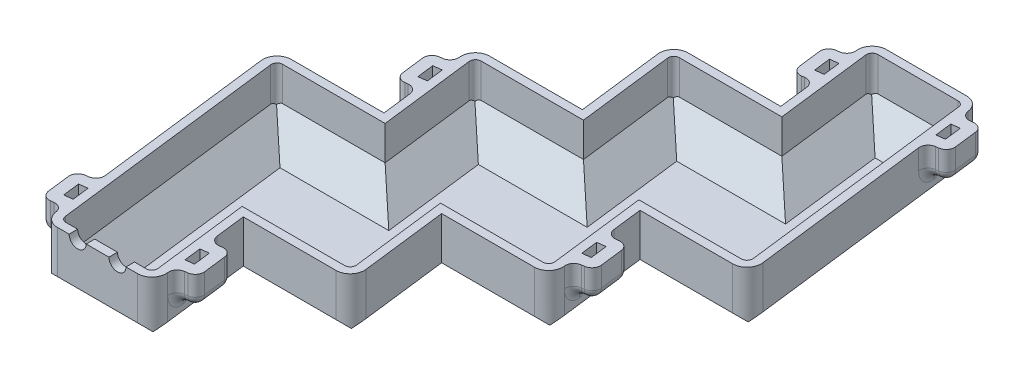
SolidWorks part; units mm, degrees
ref_plane "Front Plane" through (0, 0, 0) normal (0, 0, 1) x (1, 0, 0)
ref_plane "Top Plane" through (0, 0, 0) normal (0, 1, 0) x (1, 0, 0)
ref_plane "Right Plane" through (0, 0, 0) normal (1, 0, 0) x (0, 0, -1)
sketch "Sketch1" plane through (0, 0, 0) normal (0, 1, 0) x (1, 0, 0)
  line L12 (-24.7822, 46.1566) -> (13.5006, 46.1566)
  line L17 (-24.7822, 46.1566) -> (-13.5006, -46.1566)
  line L18 (13.5006, 46.1566) -> (24.7822, -46.1566)
  line L19 (-13.5006, -46.1566) -> (24.7822, -46.1566)
  line L20 (-5.6408, 46.1566) -> (5.6408, -46.1566) construction
  line L21 (58.6781, -10.261) -> (20.3954, -10.261)
  line L22 (58.6781, -10.261) -> (47.3965, 82.0522)
  line L23 (20.3954, -10.261) -> (9.1138, 82.0522)
  line L24 (47.3965, 82.0522) -> (9.1138, 82.0522)
  line L25 (39.5367, -10.261) -> (28.2551, 82.0522) construction
  line L26 (-58.6781, 10.261) -> (-20.3954, 10.261)
  line L27 (-58.6781, 10.261) -> (-47.3965, -82.0522)
  line L28 (-20.3954, 10.261) -> (-9.1138, -82.0522)
  line L29 (-47.3965, -82.0522) -> (-9.1138, -82.0522)
  line L30 (-39.5367, 10.261) -> (-28.2551, -82.0522) construction
  line L31 (-10.8449, -43.1566) -> (21.3932, -43.1566) construction
  line L32 (-10.8449, -43.1566) -> (-21.3932, 43.1566) construction
  line L33 (21.3932, -43.1566) -> (10.8449, 43.1566) construction
  line L34 (-21.3932, 43.1566) -> (10.8449, 43.1566) construction
  line L35 (-20.3954, 10.261) -> (20.3954, -10.261) construction
  line L36 (5.2742, -43.1566) -> (21.156, -41.2157) construction
  line L37 (-92.574, -25.6346) -> (-54.2913, -25.6346)
  line L38 (-92.574, -25.6346) -> (-81.2924, -117.9478)
  line L39 (-54.2913, -25.6346) -> (-43.0097, -117.9478)
  line L40 (-81.2924, -117.9478) -> (-43.0097, -117.9478)
  line L41 (-13.5006, -46.1566) -> (-54.2913, -25.6346) construction
  point P7 (0, 0)
  point P20 (-5.2742, 43.1566)
  point P21 (5.2742, -43.1566)
  point P26 (16.119, 0)
  point P27 (0, 0)
  point P28 (-33.8959, -35.8956)
  point P36 (-33.8959, -35.8956)
  dimension "D1" = 93
  dimension "D2" = 32
  dimension "D3" = 200
  dimension "D4" = 3
  dimension "D5" = 3
  dimension "D6" = 85
extrude "Boss-Extrude1" add sketch "Sketch1" along normal blind 25
sketch "Sketch4" plane through (0, 25, 0) normal (0, 1, 0) x (1, 0, 0)
  line L0 (-10.8449, -43.1566) -> (21.3932, -43.1566)
  line L1 (-10.8449, -43.1566) -> (-21.3932, 43.1566)
  line L2 (21.3932, -43.1566) -> (10.8449, 43.1566)
  line L3 (-21.3932, 43.1566) -> (10.8449, 43.1566)
  line L4 (23.051, -7.261) -> (55.2891, -7.261)
  line L5 (23.051, -7.261) -> (12.5027, 79.0522)
  line L6 (55.2891, -7.261) -> (44.7408, 79.0522)
  line L7 (12.5027, 79.0522) -> (44.7408, 79.0522)
  line L8 (28.6217, 79.0522) -> (39.1701, -7.261) construction
  line L9 (-55.2891, 7.261) -> (-23.051, 7.261)
  line L10 (-55.2891, 7.261) -> (-44.7408, -79.0522)
  line L11 (-23.051, 7.261) -> (-12.5027, -79.0522)
  line L12 (-44.7408, -79.0522) -> (-12.5027, -79.0522)
  line L13 (-39.1701, 7.261) -> (-28.6217, -79.0522) construction
  line L14 (-58.6781, 10.261) -> (-20.3954, 10.261) construction
  line L15 (-58.6781, 10.261) -> (-47.3965, -82.0522) construction
  line L16 (47.3965, 82.0522) -> (9.1138, 82.0522) construction
  line L17 (20.3954, -10.261) -> (9.1138, 82.0522) construction
  line L18 (-23.051, 7.261) -> (-17.0064, 7.261)
  line L19 (-10.8449, -43.1566) -> (-16.8895, -43.1566)
  line L20 (23.051, -7.261) -> (17.0064, -7.261)
  line L21 (10.8449, 43.1566) -> (16.8895, 43.1566)
  line L22 (-89.185, -28.6346) -> (-56.947, -28.6346)
  line L23 (-89.185, -28.6346) -> (-78.6367, -114.9478)
  line L24 (-56.947, -28.6346) -> (-46.3986, -114.9478)
  line L25 (-78.6367, -114.9478) -> (-46.3986, -114.9478)
  line L26 (-56.947, -28.6346) -> (-50.9023, -28.6346)
  line L27 (-44.7408, -79.0522) -> (-50.7854, -79.0522)
  line L29 (-92.574, -25.6346) -> (-54.2913, -25.6346) construction
  dimension "D1" = 3
  dimension "D2" = 3
  dimension "D3" = 3
  dimension "D4" = 3
  dimension "D5" = 3
extrude "Cut-Extrude1" cut sketch "Sketch4" against normal blind 22 contours L10 L12 L11 L9 | L19 L1 L18 L11 | L3 L1 L0 L2 | L7 L5 L4 L6 | L21 L2 L20 L5 | L23 L25 L24 L22 | L27 L10 L26 L24
chamfer "Chamfer1" distance 10 angle 45 32 edges at (39.5367, 0, 10.261) (22.5888, 0, 28.2088) (5.6408, 0, 46.1566) (-11.3072, 0, 64.1044) (-28.2551, 0, 82.0522) (-45.2031, 0, 100) (-62.151, 0, 117.9478) (-86.9332, 0, 71.7912) (-73.4326, 0, 25.6346) (-56.4847, 0, 7.6868) (-39.5367, 0, -10.261) (-22.5888, 0, -28.2088) (-5.6408, 0, -46.1566) (11.3072, 0, -64.1044) (28.2551, 0, -82.0522) (53.0373, 0, -35.8956) (-53.0957, 3, 10.6868) (50.015, 3, -35.8956) (19.1998, 3, 25.2088) (-31.6441, 3, 79.0522) (-62.5177, 3, 114.9478) (-83.9109, 3, 71.7912) (-36.1478, 3, -7.261) (-19.1998, 3, -25.2088) (-2.2518, 3, -43.1566) (14.6961, 3, -61.1044) (28.6217, 3, -79.0522) (36.1478, 3, 7.261) (2.2518, 3, 43.1566) (-14.6961, 3, 61.1044) (-48.592, 3, 97) (-70.0437, 3, 28.6346)
fillet "Fillet1" radius 2 10 edges at (55.2891, 19, 7.261) (21.3932, 19, 43.1566) (-12.5027, 19, 79.0522) (-55.2891, 19, -7.261) (-21.3932, 19, -43.1566) (12.5027, 19, -79.0522) (44.7408, 19, -79.0522) (-46.3986, 19, 114.9478) (-78.6367, 19, 114.9478) (-89.185, 19, 28.6346)
fillet "Fillet2" radius 5 10 edges at (58.6781, 17.5, 10.261) (24.7822, 17.5, 46.1566) (-9.1138, 17.5, 82.0522) (-43.0097, 17.5, 117.9478) (-81.2924, 17.5, 117.9478) (-92.574, 17.5, 25.6346) (-58.6781, 17.5, -10.261) (-24.7822, 17.5, -46.1566) (9.1138, 17.5, -82.0522) (47.3965, 17.5, -82.0522)
sketch "Sketch5" plane through (56.5791, 0, -6.9145) normal (0.9926, 0, -0.1213) x (-0.1213, 0, -0.9926)
  line L0 (-11.6551, 25) -> (71.2705, 25) construction
  line L1 (54.2705, 15) -> (68.2705, 15)
  line L2 (54.2705, 15) -> (54.2705, 25)
  line L3 (54.2705, 25) -> (68.2705, 25)
  line L4 (68.2705, 15) -> (68.2705, 25)
  line L5 (54.2705, 15) -> (68.2705, 25) construction
  line L6 (54.2705, 25) -> (68.2705, 15) construction
  line L7 (71.2705, 10) -> (71.2705, 25) construction
  point P0 (61.2705, 20)
  dimension "D1" = 3
  dimension "D2" = 14
  dimension "D3" = 10
extrude "Boss-Extrude2" add sketch "Sketch5" along normal blind 7
sketch "Sketch6" plane through (18.8597, 0, -2.3048) normal (-0.9926, 0, 0.1213) x (0.1213, 0, 0.9926)
  line L0 (-44.178, 25) -> (-74.6924, 25) construction
  line L1 (-57.6924, 15) -> (-71.6924, 15)
  line L2 (-57.6924, 15) -> (-57.6924, 25)
  line L3 (-57.6924, 25) -> (-71.6924, 25)
  line L4 (-71.6924, 15) -> (-71.6924, 25)
  line L5 (-57.6924, 15) -> (-71.6924, 25) construction
  line L6 (-57.6924, 25) -> (-71.6924, 15) construction
  line L7 (-74.6924, 25) -> (-74.6924, 10) construction
  point P0 (-64.6924, 20)
  dimension "D1" = 3
  dimension "D2" = 14
  dimension "D3" = 10
extrude "Boss-Extrude3" add sketch "Sketch6" along normal blind 7
sketch "Sketch7" plane through (-94.2984, 0, 11.5242) normal (-0.9926, 0, 0.1213) x (0.1213, 0, 0.9926)
  line L0 (19.8636, 25) -> (102.7892, 25) construction
  line L1 (85.7892, 15) -> (99.7892, 15)
  line L2 (85.7892, 15) -> (85.7892, 25)
  line L3 (85.7892, 25) -> (99.7892, 25)
  line L4 (99.7892, 15) -> (99.7892, 25)
  line L5 (85.7892, 15) -> (99.7892, 25) construction
  line L6 (85.7892, 25) -> (99.7892, 15) construction
  line L7 (102.7892, 10) -> (102.7892, 25) construction
  point P0 (92.7892, 20)
  dimension "D1" = 3
  dimension "D2" = 14
  dimension "D3" = 10
extrude "Boss-Extrude4" add sketch "Sketch7" along normal blind 7
sketch "Sketch8" plane through (-56.5791, 0, 6.9145) normal (0.9926, 0, -0.1213) x (-0.1213, 0, -0.9926)
  line L0 (-75.6967, 25) -> (-106.2111, 25) construction
  line L1 (-89.2111, 15) -> (-103.2111, 15)
  line L2 (-89.2111, 15) -> (-89.2111, 25)
  line L3 (-89.2111, 25) -> (-103.2111, 25)
  line L4 (-103.2111, 15) -> (-103.2111, 25)
  line L5 (-89.2111, 15) -> (-103.2111, 25) construction
  line L6 (-89.2111, 25) -> (-103.2111, 15) construction
  line L7 (-106.2111, 25) -> (-106.2111, 10) construction
  point P0 (-96.2111, 20)
  dimension "D1" = 3
  dimension "D2" = 10
  dimension "D3" = 14
extrude "Boss-Extrude5" add sketch "Sketch8" along normal blind 7
sketch "Sketch9" plane through (18.8597, 0, -2.3048) normal (0.9926, 0, -0.1213) x (-0.1213, 0, -0.9926)
  line L0 (-12.6593, 25) -> (-43.1737, 25) construction
  line L1 (-26.1737, 15) -> (-40.1737, 15)
  line L2 (-26.1737, 15) -> (-26.1737, 25)
  line L3 (-26.1737, 25) -> (-40.1737, 25)
  line L4 (-40.1737, 15) -> (-40.1737, 25)
  line L5 (-26.1737, 15) -> (-40.1737, 25) construction
  line L6 (-26.1737, 25) -> (-40.1737, 15) construction
  line L7 (-43.1737, 25) -> (-43.1737, 10) construction
  point P0 (-33.1737, 20)
  dimension "D1" = 3
  dimension "D2" = 14
  dimension "D3" = 10
extrude "Boss-Extrude6" add sketch "Sketch9" along normal blind 7
sketch "Sketch10" plane through (-56.5791, 0, 6.9145) normal (-0.9926, 0, 0.1213) x (0.1213, 0, 0.9926)
  line L0 (-11.6551, 25) -> (18.8594, 25) construction
  line L1 (5.3449, 15) -> (-8.6551, 15)
  line L2 (5.3449, 15) -> (5.3449, 25)
  line L3 (5.3449, 25) -> (-8.6551, 25)
  line L4 (-8.6551, 15) -> (-8.6551, 25)
  line L5 (5.3449, 15) -> (-8.6551, 25) construction
  line L6 (5.3449, 25) -> (-8.6551, 15) construction
  line L7 (-11.6551, 25) -> (-11.6551, 10) construction
  point P0 (-1.6551, 20)
  dimension "D1" = 3
  dimension "D2" = 14
  dimension "D3" = 10
extrude "Boss-Extrude7" add sketch "Sketch10" along normal blind 7
sketch "Sketch11" plane through (0, 25, 0) normal (0, 1, 0) x (1, 0, 0)
  line L0 (-86.3842, -101.0143) -> (-83.4063, -100.6503)
  line L1 (-86.3842, -101.0143) -> (-85.6563, -106.97)
  line L2 (-83.4063, -100.6503) -> (-82.6785, -106.606)
  line L3 (-85.6563, -106.97) -> (-82.6785, -106.606)
  line L4 (-45.2718, -99.4373) -> (-42.294, -99.0733)
  line L5 (-91.8888, -31.2411) -> (-83.8915, -96.6799) construction
  line L6 (-90.8399, -97.529) -> (-83.8915, -96.6799) construction
  line L7 (-45.2718, -99.4373) -> (-44.544, -105.393)
  line L8 (-42.294, -99.0733) -> (-41.5662, -105.029)
  line L9 (-44.544, -105.393) -> (-41.5662, -105.029)
  line L12 (-47.3965, -82.0522) -> (-45.7571, -95.4668) construction
  line L13 (-38.8088, -94.6177) -> (-45.7571, -95.4668) construction
  line L14 (-60.1216, -2.6578) -> (-57.1437, -2.2938)
  line L15 (-60.1216, -2.6578) -> (-59.3937, -8.6135)
  line L16 (-57.1437, -2.2938) -> (-56.4159, -8.2495)
  line L17 (-59.3937, -8.6135) -> (-56.4159, -8.2495)
  line L18 (-55.9307, -12.22) -> (-54.2913, -25.6346) construction
  line L19 (-64.5773, 0.8275) -> (-57.629, 1.6766) construction
  line L20 (-62.879, -13.0692) -> (-55.9307, -12.22) construction
  line L21 (22.52, -27.6461) -> (25.4978, -27.2821)
  line L22 (22.52, -27.6461) -> (23.2478, -33.6018)
  line L23 (25.4978, -27.2821) -> (26.2257, -33.2378)
  line L24 (23.2478, -33.6018) -> (26.2257, -33.2378)
  line L25 (20.3954, -10.261) -> (22.0348, -23.6756) construction
  line L26 (28.9831, -22.8265) -> (22.0348, -23.6756) construction
  line L27 (7.6702, 69.1334) -> (10.6481, 69.4974)
  line L28 (7.6702, 69.1334) -> (8.3981, 63.1777)
  line L29 (10.6481, 69.4974) -> (11.3759, 63.5417)
  line L30 (8.3981, 63.1777) -> (11.3759, 63.5417)
  line L31 (48.7826, 70.7104) -> (51.7604, 71.0744)
  line L32 (48.7826, 70.7104) -> (49.5104, 64.7547)
  line L33 (51.7604, 71.0744) -> (52.4882, 65.1187)
  line L34 (49.5104, 64.7547) -> (52.4882, 65.1187)
  line L35 (57.9929, -4.6545) -> (49.9956, 60.7843) construction
  line L36 (13.5006, 46.1566) -> (11.8612, 59.5712) construction
  line L39 (3.2146, 72.6187) -> (10.1629, 73.4678) construction
  line L40 (55.2456, 75.53) -> (48.2973, 74.6809) construction
  dimension "D1" = 4
  dimension "D2" = 3
  dimension "D3" = 6
  dimension "D4" = 4
  dimension "D5" = 4
  dimension "D6" = 4
  dimension "D7" = 4
  dimension "D8" = 4
extrude "Cut-Extrude2" cut sketch "Sketch11" against normal through all
fillet "Fillet3" radius 3 54 edges at (-83.6489, 15, 98.6651) (-82.4359, 15, 108.5913) (-90.8399, 20, 97.529) (-87.3657, 15, 97.1045) (-83.8915, 20, 96.6799) (-89.9907, 15, 104.4773) (-89.1415, 20, 111.4256) (-85.6674, 15, 111.0011) (-82.1932, 20, 110.5765) (-44.0588, 20, 109.3634) (-45.7571, 20, 95.4668) (23.7331, 20, 37.5722) (22.0348, 20, 23.6756) (49.9956, 20, -60.7843) (48.2973, 20, -74.6809) (11.8612, 20, -59.5712) (10.1629, 20, -73.4678) (-57.629, 20, -1.6766) (-55.9307, 20, 12.22) (-40.5846, 15, 108.9388) (-37.1105, 20, 108.5143) (-44.3014, 15, 107.3782) (-45.5145, 15, 97.452) (-38.8088, 20, 94.6177) (-37.9596, 15, 101.566) (-42.2829, 15, 95.0422) (30.6814, 20, 36.7231) (27.2072, 15, 37.1476) (23.4904, 15, 35.587) (28.9831, 20, 22.8265) (29.8322, 15, 29.7748) (22.2774, 15, 25.6608) (25.5089, 15, 23.251) (56.9439, 20, -61.6334) (53.4698, 15, -61.2089) (49.753, 15, -62.7695) (48.5399, 15, -72.6957) (51.7715, 15, -75.1055) (56.0948, 15, -68.5817) (55.2456, 20, -75.53) (4.9129, 20, -58.7221) (8.387, 15, -59.1466) (4.0637, 15, -65.6704) (3.2146, 20, -72.6187) (6.6887, 15, -73.0432) (10.4055, 15, -71.4826) (11.6185, 15, -61.5564) (-61.1031, 15, -1.252) (-64.5773, 20, -0.8275) (-57.3864, 15, 0.3086) (-56.1733, 15, 10.2348) (-63.7281, 15, 6.1208) (-62.879, 20, 13.0692) (-59.4048, 15, 12.6446)
sketch "Sketch12" plane through (0, 0, 117.9478) normal (0, 0, 1) x (1, 0, 0)
  line L0 (-76.8662, 25) -> (-48.6579, 25) construction
  line L1 (-62.7621, 25) -> (-62.7621, 26.8313) construction
  circle A0 centre (-69.7621, 25) radius 3
  circle A1 centre (-55.7621, 25) radius 3
  dimension "D1" = 6
  dimension "D2" = 7
extrude "Cut-Extrude3" cut sketch "Sketch12" against normal blind 10
sketch "Sketch13" plane through (0, 0, -82.0522) normal (0, 0, -1) x (-1, 0, 0)
  line L0 (-28.8662, 25) -> (-28.8662, 10) construction
  line L1 (-42.9703, 25) -> (-14.762, 25) construction
  line L2 (-42.9703, 10) -> (-14.762, 10) construction
  text T0 "<r180>R</r>" font "Century Gothic" height 3.5
  point P7 (-26.9367, 19.9363)
  point P8 (0, 0)
extrude "Cut-Extrude4" cut sketch "Sketch13" against normal blind 1
equation "\"D7@Sketch11\"=\"D5@Sketch11\""
equation "\"D8@Sketch11\"=\"D5@Sketch11\""
equation "\"D6@Sketch11\"=\"D5@Sketch11\""
equation "\"D5@Sketch11\"=\"D1@Sketch11\""
equation "\"D4@Sketch11\"=\"D1@Sketch11\""
